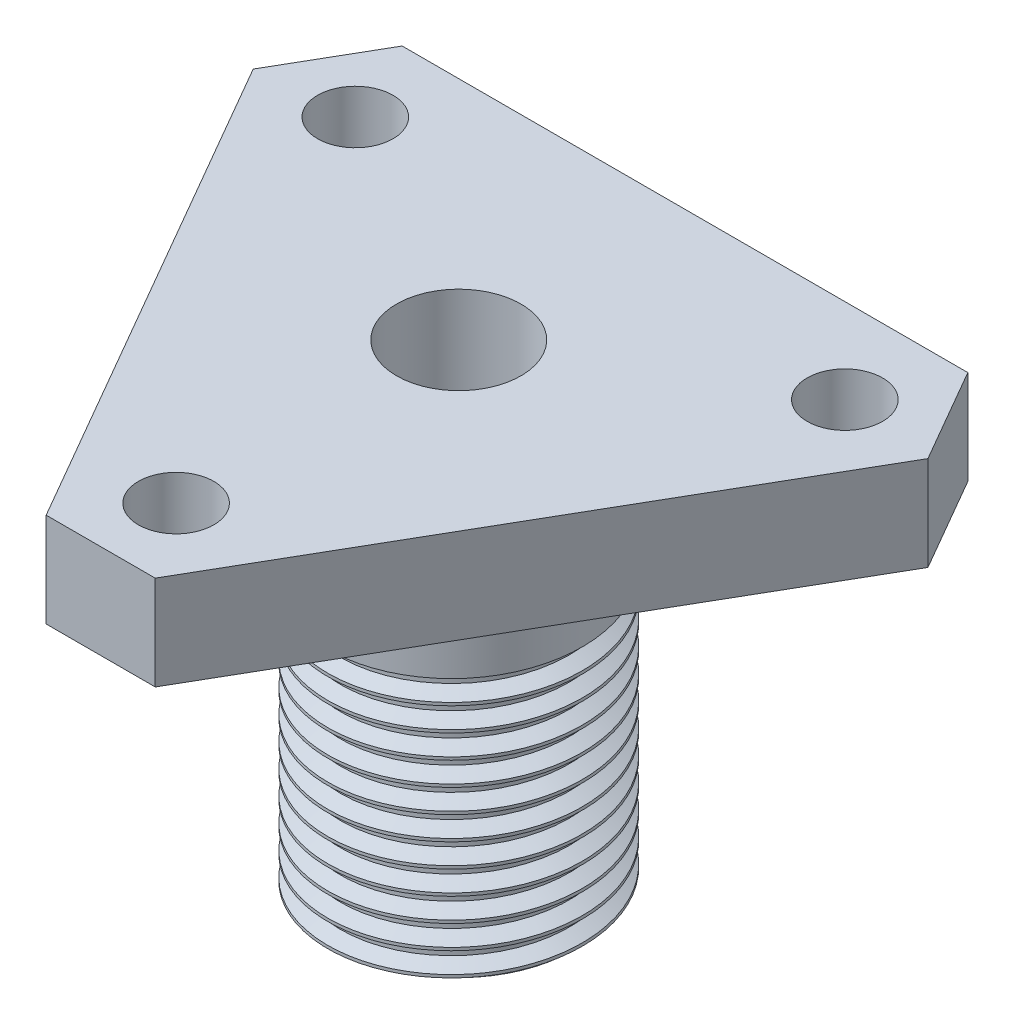
SolidWorks part; units mm, degrees
material "Nylon 101"
ref_plane "Plan de face" through (0, 0, 0) normal (0, 0, 1) x (1, 0, 0)
ref_plane "Plan de dessus" through (0, 0, 0) normal (0, 1, 0) x (1, 0, 0)
ref_plane "Plan de droite" through (0, 0, 0) normal (1, 0, 0) x (0, 0, -1)
sketch "Esquisse1" plane through (0, 0, 0) normal (0, 0, 1) x (1, 0, 0)
  line L0 (0, 0) -> (0, 20)
  line L1 (0, 0) -> (5.25, 0)
  line L2 (5.25, 0) -> (5.25, 20) construction
  line L3 (5.25, 20) -> (6.75, 20)
  line L4 (6.75, 20) -> (6.75, 0)
  line L5 (6.75, 0) -> (5.25, 0)
  line L6 (0, 20) -> (5.25, 20)
  dimension "D1" = 20
  dimension "D2" = 5.25
  dimension "D3" = 1.5
revolve "Révolution1" add sketch "Esquisse1" angle 360 about L0
thread "Filetage1" pitch 1.25 method cut profile "Profil de filetage1" start angle 0, offset 5, length 22, pitch 1.25, diameter 13.5
ref_plane "Plan1" through (-6.75, 15, 0) normal (0, 0, 1) x (-1, 0, 0)
sketch "Profil de filetage1" plane through (-6.75, 15, 0) normal (0, 0, 1) x (-1, 0, 0)
  line L0 (0, 0) -> (0, 1.25) construction
  line L11 (0, 0) -> (0, 1.0937)
  line L12 (0, 1.0937) -> (-0.6766, 0.7031)
  line L13 (-0.6766, 0.7031) -> (-0.6766, 0.3906)
  line L15 (-0.6766, 0.3906) -> (0, 0)
  line L17 (-0.6766, 0.5469) -> (0, 0.5469) construction
  point P2 (0, 0)
  dimension "Pitch" = 1.25
  dimension "Profile_Angle" = 60
  dimension "Profile_Land" = 0.3125
  dimension "Profile_Height" = 0.6766
sketch "Esquisse2" plane through (0, 0, 0) normal (0, 1, 0) x (1, 0, 0)
  line L5 (0, 0) -> (0, 12) construction
  line L6 (15, 12) -> (-15, 12)
  line L10 (2.8923, -18.9904) -> (17.8923, 6.9904)
  line L11 (0, 0) -> (10.3923, -6) construction
  line L12 (-17.8923, 6.9904) -> (-2.8923, -18.9904)
  line L13 (0, 0) -> (-10.3923, -6) construction
  line L14 (-15, 12) -> (-17.8923, 6.9904)
  line L15 (-2.8923, -18.9904) -> (2.8923, -18.9904)
  line L16 (17.8923, 6.9904) -> (15, 12)
  point P6 (0, 12)
  point P15 (0, 0)
  dimension "D1" = 30
  dimension "D2" = 3
  dimension "D3" = 12
extrude "Boss.-Extru.1" add sketch "Esquisse2" along normal blind 5 from surface starting at face at (0, 20, -6.75)
sketch "Esquisse3" plane through (0, 0, 0) normal (0, 1, 0) x (1, 0, 0)
  line L0 (0, 0) -> (3.3, 0) construction
  line L1 (0, 0) -> (0, 3.3) construction
  line L2 (-16.4462, 9.4952) -> (0, 0) construction
  line L5 (-17.8923, 6.9904) -> (-15, 12) construction
  line L6 (0, 0) -> (16.4462, 9.4952) construction
  line L7 (15, 12) -> (17.8923, 6.9904) construction
  line L8 (0, 0) -> (0, -18.9904) construction
  line L9 (2.8923, -18.9904) -> (-2.8923, -18.9904) construction
  circle A0 centre (0, 0) radius 3.3
  circle A5 centre (-12.9821, 7.4952) radius 2
  circle A7 centre (12.9821, 7.4952) radius 2
  circle A8 centre (0, -14.9904) radius 2
  point P16 (0, 0)
  point P23 (0, 0)
  dimension "D1" = 6.6
  dimension "D3" = 4
  dimension "D2" = 4
  dimension "D4" = 3
extrude "Enlèv. mat.-Extru.3" cut sketch "Esquisse3" against normal through all and the other way through all
